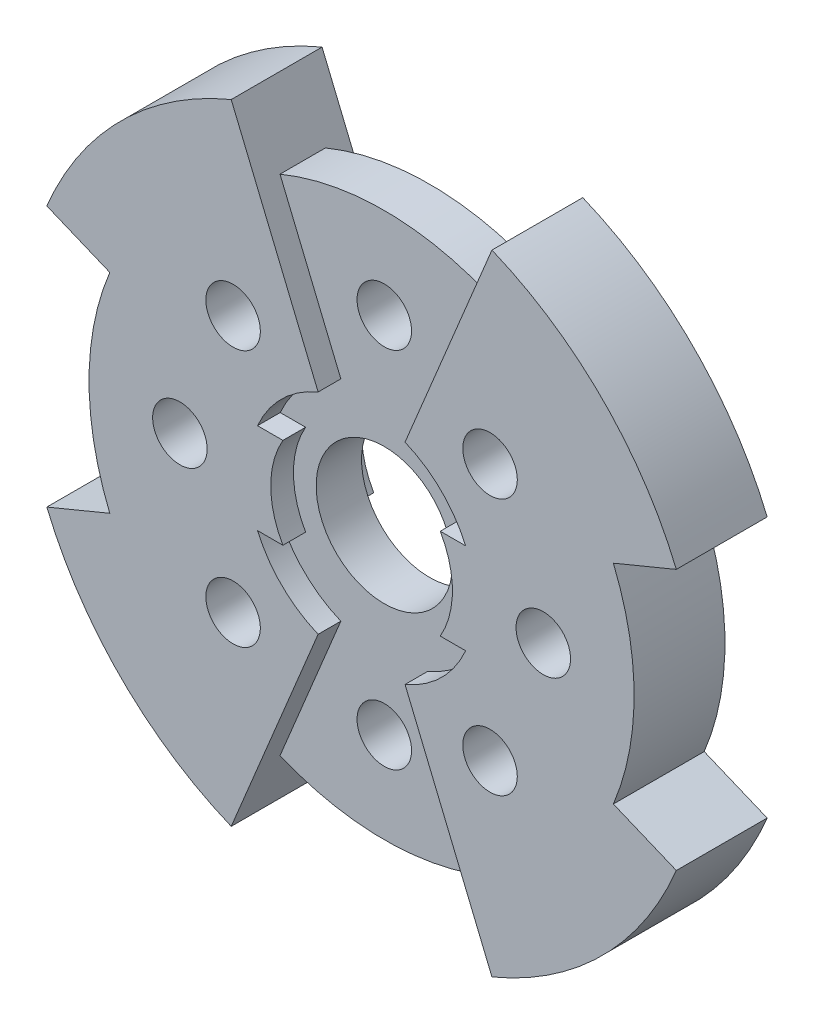
SolidWorks part; units mm, degrees
ref_plane "Front Plane" through (0, 0, 0) normal (0, 0, 1) x (1, 0, 0)
ref_plane "Top Plane" through (0, 0, 0) normal (0, 1, 0) x (1, 0, 0)
ref_plane "Right Plane" through (0, 0, 0) normal (1, 0, 0) x (0, 0, -1)
sketch "Sketch1" plane through (0, 0, 0) normal (0, 0, 1) x (1, 0, 0)
  line L0 (0, 0) -> (0, 40780.4257) construction
  line L1 (0, 0) -> (40780.4257, 0) construction
  line L2 (9.5671, 23.097) -> (28.7013, 69.291)
  line L3 (-9.5671, 23.097) -> (0, 0) construction
  line L4 (17.3205, -10) -> (22.9129, -10)
  line L5 (17.3205, 10) -> (22.9129, 10)
  line L6 (0, 0) -> (9.5671, 23.097) construction
  line L7 (-9.5671, 23.097) -> (-28.7013, 69.291)
  line L8 (-9.5671, -23.097) -> (-28.7013, -69.291)
  line L9 (9.5671, -23.097) -> (28.7013, -69.291)
  line L10 (-17.3205, -10) -> (-22.9129, -10)
  line L11 (-17.3205, 10) -> (-22.9129, 10)
  line L12 (55.4328, 22.961) -> (0, 0) construction
  line L13 (55.4328, -22.961) -> (69.291, -28.7013)
  line L14 (55.4328, 22.961) -> (69.291, 28.7013)
  line L15 (0, 0) -> (55.4328, -22.961) construction
  line L16 (-55.4328, -22.961) -> (-69.291, -28.7013)
  line L17 (-55.4328, 22.961) -> (-69.291, 28.7013)
  circle A0 centre (0, 0) radius 15
  arc A1 (-22.9129, -10) -> (-9.5671, -23.097) centre (0, 0) ccw
  circle A2 centre (0, 0) radius 40 construction
  arc A3 (-22.961, -55.4328) -> (22.961, -55.4328) centre (0, 0) ccw
  arc A4 (-28.7013, 69.291) -> (-69.291, 28.7013) centre (0, 0) ccw
  arc A5 (-17.3205, 10) -> (-17.3205, -10) centre (0, 0) ccw
  arc A6 (22.9129, 10) -> (9.5671, 23.097) centre (0, 0) ccw
  arc A7 (-9.5671, 23.097) -> (-22.9129, 10) centre (0, 0) ccw
  arc A8 (9.5671, -23.097) -> (22.9129, -10) centre (0, 0) ccw
  arc A9 (17.3205, -10) -> (17.3205, 10) centre (0, 0) ccw
  arc A10 (28.7013, -69.291) -> (69.291, -28.7013) centre (0, 0) ccw
  circle A11 centre (0, 40) radius 6
  circle A12 centre (28.2843, 28.2843) radius 6
  circle A13 centre (40, 0) radius 6
  circle A14 centre (28.2843, -28.2843) radius 6
  circle A15 centre (0, -40) radius 6
  circle A16 centre (-28.2843, -28.2843) radius 6
  circle A17 centre (-40, 0) radius 6
  circle A18 centre (-28.2843, 28.2843) radius 6
  arc A19 (69.291, 28.7013) -> (28.7013, 69.291) centre (0, 0) ccw
  arc A20 (-69.291, -28.7013) -> (-28.7013, -69.291) centre (0, 0) ccw
  arc A21 (-55.4328, 22.961) -> (-55.4328, -22.961) centre (0, 0) ccw
  arc A22 (22.961, 55.4328) -> (-22.961, 55.4328) centre (0, 0) ccw
  arc A23 (55.4328, -22.961) -> (55.4328, 22.961) centre (0, 0) ccw
  point P15 (55.4677, 23.097)
  point P45 (0, 0)
  dimension "D1" = 30
  dimension "D2" = 50
  dimension "D3" = 80
  dimension "D4" = 120
  dimension "D5" = 150
  dimension "D6" = 40
  dimension "D7" = 20
  dimension "D9" = 12
  dimension "D8" = 45
  dimension "D11" = 45
  dimension "D10" = 8
extrude "Boss-Extrude1" add sketch "Sketch1" along normal mid plane 20 contours L17 A21 L16 A20 L8 A1 L10 A5 L11 A7 L7 A4 A16 A17 A18 | L13 A23 L14 A19 L2 A6 L5 A9 L4 A8 L9 A10 A12 A13 A14 region at (17.6582, 38.6874, 0) region at (-17.6582, 38.6874, 0)
extrude "Boss-Extrude2" add sketch "Sketch1<3>" along normal mid plane 10 contours L2 A22 L7 A7 L11 A5 L10 A1 L8 A3 L9 A8 L4 A9 L5 A6 A0 A11 A15 region at (16.6106, 16.9262, 0)
sketch "Sketch1<3>" plane through (0, 0, 0) normal (0, 0, 1) x (1, 0, 0) same geometry as "Sketch1"
